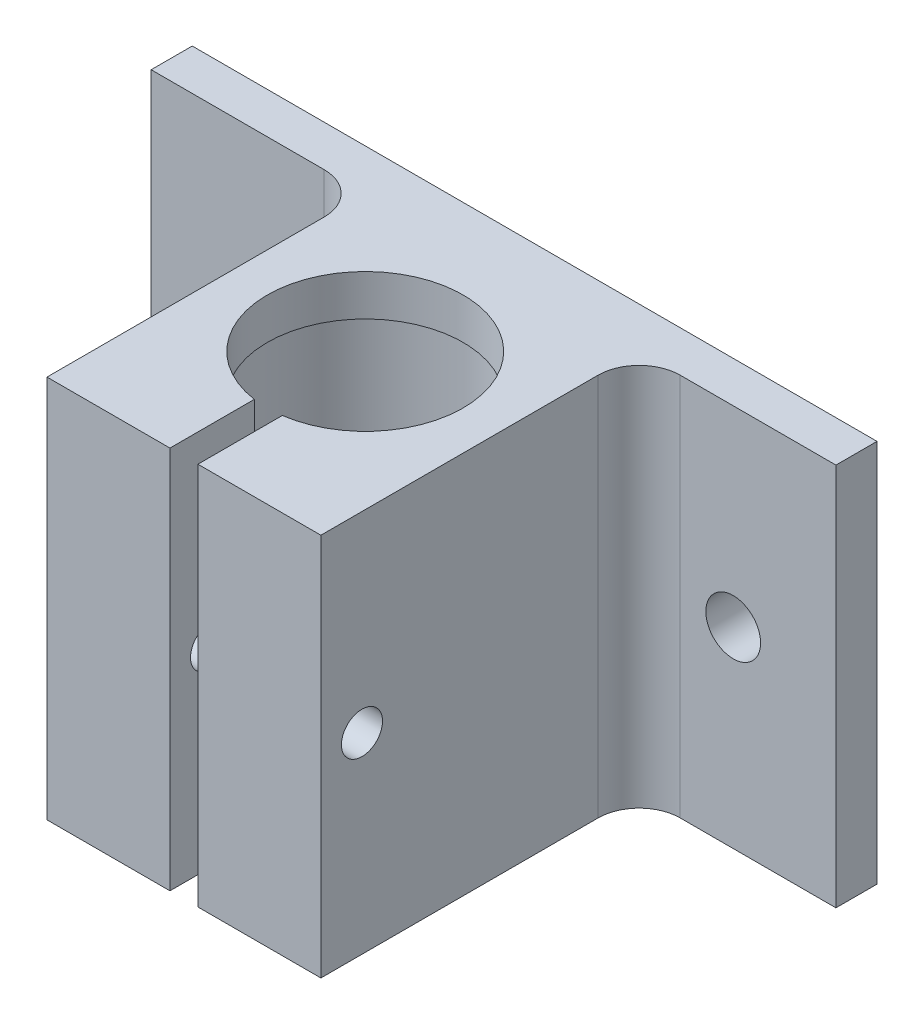
SolidWorks part; units mm, degrees
ref_plane "Front Plane" through (0, 0, 0) normal (0, 0, 1) x (1, 0, 0)
ref_plane "Top Plane" through (0, 0, 0) normal (0, 1, 0) x (1, 0, 0)
ref_plane "Right Plane" through (0, 0, 0) normal (1, 0, 0) x (0, 0, -1)
sketch "Sketch1" plane through (0, 0, 0) normal (0, 1, 0) x (1, 0, 0)
  line L1 (-25.6311, 10) -> (-10, 10)
  line L2 (-25.6311, 10) -> (-25.6311, 13)
  line L3 (-25.6311, 13) -> (24.3689, 13)
  line L4 (24.3689, 10) -> (24.3689, 13)
  line L10 (1.0214, -13.238) -> (10, -13.238)
  line L12 (-10, 10) -> (-10, -13.238)
  line L13 (-10, -13.238) -> (-1.0214, -13.238)
  line L14 (10, 10) -> (10, -13.238)
  line L16 (-1.0214, -13.238) -> (-1.0214, -7.0767)
  line L19 (1.0214, -13.238) -> (1.0214, -7.0767)
  line L20 (10, 10) -> (24.3689, 10)
  arc A0 (1.0214, -7.0767) -> (-1.0214, -7.0767) centre (0, 0) ccw
  point P3 (-0.6311, 16.5)
  dimension "D1" = 14.3
  dimension "D2" = 3
  dimension "D3" = 50
  dimension "D4" = 10
  dimension "D5" = 20
  dimension "D6" = 10
extrude "Boss-Extrude1" add sketch "Sketch1" along normal blind 28
sketch "Sketch2" plane through (-10, 0, 0) normal (-1, 0, 0) x (0, 0, 1)
  line L0 (13.238, 28) -> (13.238, 0) construction
  circle A0 centre (10.238, 14) radius 1.5
  dimension "D1" = 3
  dimension "D2" = 3
extrude "Cut-Extrude1" cut sketch "Sketch2" against normal blind 20
sketch "Sketch3" plane through (-10, 0, 0) normal (-1, 0, 0) x (0, 0, 1)
  line L7 (10.238, 17.1754) -> (7.488, 15.5877)
  line L8 (7.488, 15.5877) -> (7.488, 12.4123)
  line L9 (7.488, 12.4123) -> (10.238, 10.8246)
  line L10 (10.238, 10.8246) -> (12.988, 12.4123)
  line L11 (12.988, 12.4123) -> (12.988, 15.5877)
  line L12 (12.988, 15.5877) -> (10.238, 17.1754)
  circle A0 centre (10.238, 14) radius 2.75 construction
  dimension "D1" = 5.5
extrude "Cut-Extrude2" cut sketch "Sketch3" against normal blind 2
sketch "Sketch4" plane through (0, 0, -13) normal (0, 0, -1) x (-1, 0, 0)
  line L0 (0, 0) -> (0, 34.3534) construction
  line L1 (-24.3689, 14) -> (30.6657, 14) construction
  line L2 (-24.3689, 28) -> (-24.3689, 0) construction
  circle A0 centre (-16.8689, 14) radius 2
  circle A1 centre (16.8689, 14) radius 2
  dimension "D1" = 4
  dimension "D2" = 7.5
extrude "Cut-Extrude3" cut sketch "Sketch4" against normal blind 3
fillet "Fillet1" radius 3 1 edges at (10, 14, -10)
fillet "Fillet2" radius 3 1 edges at (-10, 14, -10)
sketch "Sketch5" plane through (0, 0, 0) normal (0, -1, 0) x (1, 0, 0)
  circle A0 centre (0, 0) radius 7.75
  dimension "D1" = 15.5
extrude "Cut-Extrude4" cut sketch "Sketch5" against normal blind 25
